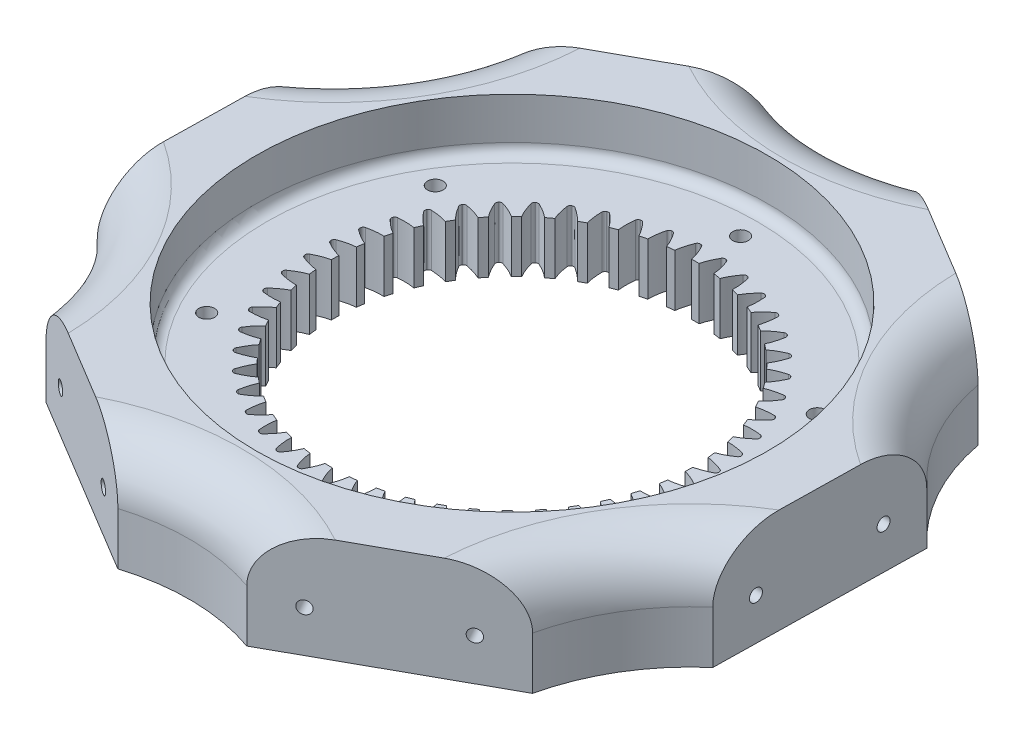
SolidWorks part; units mm, degrees
material "ABS"
ref_plane "Plan de face" through (0, 0, 0) normal (0, 0, 1) x (1, 0, 0)
ref_plane "Plan de dessus" through (0, 0, 0) normal (0, 1, 0) x (1, 0, 0)
ref_plane "Plan de droite" through (0, 0, 0) normal (1, 0, 0) x (0, 0, -1)
sketch "Esquisse1" plane through (0, 0, 0) normal (0, 1, 0) x (1, 0, 0)
  circle A0 centre (0, 0) radius 37.875
  circle A1 centre (0, 0) radius 34.5 construction
  circle A2 centre (0, 0) radius 36 construction
  circle A6 centre (0, 0) radius 33.8289 construction
  dimension "D1" = 72
  dimension "D5" = 1.875
  dimension "D6" = 1.5
  dimension "D7" = 67.6579
  dimension "D11" = 75.75
extrude "Boss.-Extru.1" add sketch "Esquisse1" along normal blind 10
sketch "Esquisse3" plane through (0, 0, 0) normal (0, 1, 0) x (1, 0, 0)
  spline S2 degree 4 poles (33.8289, 0) (33.8539, 0.0005) (33.924, 0.0037) (34.0563, 0.016) (34.2711, 0.0454) (34.5432, 0.0961) (34.8923, 0.177) (35.2997, 0.2918) (35.7425, 0.4383) (36.2181, 0.6191) (36.6866, 0.8186) (37.1478, 1.0347) (37.6016, 1.2659) (38.1432, 1.5633) (38.7827, 1.9461) (39.5113, 2.4268) (40.3185, 3.017) (41.1123, 3.6556) (41.8778, 4.3274) (42.6156, 5.0301) (43.2366, 5.6687) (43.7524, 6.2332) (44.2535, 6.8077) (44.662, 7.2997) (45.055, 7.7938) (45.4439, 8.3074) (45.7379, 8.7068) (46.0457, 9.1427) (46.3102, 9.5258) (46.689, 10.0991) (46.9096, 10.4462) (47.2576, 11.0073) (47.4044, 11.2615) (47.541, 11.4906) (47.5789, 11.5586) (47.6078, 11.6082) (47.6235, 11.635) knots 0 0 0 0 0 0.005377 0.015084 0.028532 0.04661 0.064855 0.092111 0.119476 0.146842 0.174209 0.201575 0.228941 0.256307 0.307035 0.361767 0.4165 0.471232 0.525964 0.580697 0.635429 0.662795 0.690161 0.744894 0.77226 0.799626 0.826992 0.854358 0.881725 0.909091 0.954545 0.977273 0.988636 0.994318 1 1 1 1 1 construction
  spline S3 degree 4 poles (33.8289, 0) (33.8539, 0.0005) (33.924, 0.0037) (34.0563, 0.016) (34.2711, 0.0454) (34.5432, 0.0961) (34.8923, 0.177) (35.2997, 0.2918) (35.7425, 0.4383) (36.2181, 0.6191) (36.6866, 0.8186) (37.1478, 1.0347) (37.6016, 1.2659) (38.1432, 1.5633) (38.7827, 1.9461) (39.5113, 2.4268) (40.3185, 3.017) (41.1123, 3.6556) (41.8778, 4.3274) (42.6156, 5.0301) (43.2366, 5.6687) (43.7524, 6.2332) (44.2535, 6.8077) (44.662, 7.2997) (45.055, 7.7938) (45.4439, 8.3074) (45.7379, 8.7068) (46.0457, 9.1427) (46.3102, 9.5258) (46.554, 9.8948) (46.6814, 10.0908) (46.7439, 10.1882) knots 0 0 0 0 0 0.005377 0.015084 0.028532 0.04661 0.064855 0.092111 0.119476 0.146842 0.174209 0.201575 0.228941 0.256307 0.307035 0.361767 0.4165 0.471232 0.525964 0.580697 0.635429 0.662795 0.690161 0.744894 0.77226 0.799626 0.826992 0.854358 0.881725 0.909091 0.909091 0.909091 0.909091 0.909091
sketch "Esquisse5" plane through (0, 0, 0) normal (0, 1, 0) x (1, 0, 0)
  line L0 (0, 0) -> (35.9943, -0.6415) construction
  circle A0 centre (0, 0) radius 34.5 construction
  arc A1 (34.4748, -1.3194) -> (34.4999, 0.0901) centre (0, 0) ccw
  circle A2 centre (0, 0) radius 36 construction
  spline S1 degree 4 poles (25.7599, 1999.7824) (28.1484, 36.3806) (30.2572, 0.6765) (32.2943, -0.2246) (34.2711, 0.0454) (34.5432, 0.0961) (34.8923, 0.177) (35.2997, 0.2918) (35.7425, 0.4383) (36.2181, 0.6191) (36.6866, 0.8186) (37.1478, 1.0347) (37.6016, 1.2659) (38.1432, 1.5633) (38.7827, 1.9461) (39.5113, 2.4268) (40.3185, 3.017) (41.1123, 3.6556) (41.8778, 4.3274) (42.6156, 5.0301) (43.2366, 5.6687) (43.7524, 6.2332) (44.2535, 6.8077) (44.662, 7.2997) (45.055, 7.7938) (45.4439, 8.3074) (45.7379, 8.7068) (46.0457, 9.1427) (47.3684, 11.0587) (50.4497, 16.1577) (14.6278, -39.0088) (1126.5221, 1693.5325) knots -0.382222 -0.382222 -0.382222 -0.382222 -0.382222 0.005377 0.015084 0.028532 0.04661 0.064855 0.092111 0.119476 0.146842 0.174209 0.201575 0.228941 0.256307 0.307035 0.361767 0.4165 0.471232 0.525964 0.580697 0.635429 0.662795 0.690161 0.744894 0.77226 0.799626 0.826992 0.854358 0.881725 1.347109 1.347109 1.347109 1.347109 1.347109 only from (33.8289, 0) to (46.7439, 10.1882) construction
  spline S2 degree 4 poles (34.4999, 0.0901) (34.5463, 0.0995) (34.6757, 0.127) (34.9277, 0.187) (35.2997, 0.2918) (35.7425, 0.4383) (36.2181, 0.6191) (36.6866, 0.8186) (37.1478, 1.0347) (37.6016, 1.2659) (38.1432, 1.5633) (38.7827, 1.9461) (39.5113, 2.4268) (40.3185, 3.017) (41.1123, 3.6556) (41.8778, 4.3274) (42.6156, 5.0301) (43.2366, 5.6687) (43.7524, 6.2332) (44.2535, 6.8077) (44.662, 7.2997) (45.055, 7.7938) (45.4439, 8.3074) (45.7379, 8.7068) (46.0457, 9.1427) (46.3102, 9.5258) (46.554, 9.8948) (46.6814, 10.0908) (46.7439, 10.1882) knots 0.036425 0.036425 0.036425 0.036425 0.036425 0.04661 0.064855 0.092111 0.119476 0.146842 0.174209 0.201575 0.228941 0.256307 0.307035 0.361767 0.4165 0.471232 0.525964 0.580697 0.635429 0.662795 0.690161 0.744894 0.77226 0.799626 0.826992 0.854358 0.881725 0.909091 0.909091 0.909091 0.909091 0.909091
  spline S3 degree 4 poles (34.4748, -1.3194) (34.5208, -1.3304) (34.6491, -1.3626) (34.8988, -1.4315) (35.2669, -1.5495) (35.7041, -1.7116) (36.173, -1.9093) (36.6342, -2.1253) (37.0873, -2.3577) (37.5326, -2.6049) (38.0633, -2.9215) (38.6887, -3.3269) (39.3997, -3.8332) (40.1854, -4.4518) (40.956, -5.1183) (41.697, -5.8169) (42.4093, -6.5455) (43.0071, -7.2058) (43.5025, -7.7883) (43.9828, -8.3803) (44.3736, -8.8866) (44.7487, -9.3943) (45.119, -9.9215) (45.3986, -10.3311) (45.6907, -10.7776) (45.9413, -11.1699) (46.1718, -11.5474) (46.2922, -11.7479) (46.3512, -11.8474) knots 0.036425 0.036425 0.036425 0.036425 0.036425 0.04661 0.064855 0.092111 0.119476 0.146842 0.174209 0.201575 0.228941 0.256307 0.307035 0.361767 0.4165 0.471232 0.525964 0.580697 0.635429 0.662795 0.690161 0.744894 0.77226 0.799626 0.826992 0.854358 0.881725 0.909091 0.909091 0.909091 0.909091 0.909091
  point P6 (35.996, 0.5365)
  dimension "D1" = 1.875
extrude "Enlèv. mat.-Extru.1" cut sketch "Esquisse5" against normal through all and the other way through all
fillet "Congé1" radius 0.57 2 edges at (37.775, 5, 2.751) (37.849, 5, -1.4032)
pattern_circular "Répétition circulaire1" count 48 over 360 about axis through (0, 10, 0) along (0, 1, 0) of "Enlèv. mat.-Extru.1", "Congé1"
sketch "Esquisse6" plane through (0, 0, 0) normal (0, -1, 0) x (1, 0, 0)
  circle A0 centre (0, 0) radius 49
  circle A1 centre (0, 0) radius 37.875 construction
  dimension "D1" = 11.125
  dimension "D2" = 98
extrude "Boss.-Extru.2" add sketch "Esquisse6" against normal up to surface (10 mm away) separate body up to face at (0, 10, 0)
combine bodies "Combiner1" operation type subtract main body 106 bodies to subtract 105
sketch "Esquisse8" plane through (0, 0, 0) normal (0, 1, 0) x (1, 0, 0)
  line L0 (-59.3732, 35.7047) -> (59.3732, -35.7047) construction
  line L1 (1.2346, 69.271) -> (-59.3732, 35.7047)
  line L2 (-59.3732, 35.7047) -> (-60.6078, -33.5663)
  line L3 (-60.6078, -33.5663) -> (-1.2346, -69.271)
  line L4 (-1.2346, -69.271) -> (59.3732, -35.7047)
  line L5 (59.3732, -35.7047) -> (60.6078, 33.5663)
  line L6 (60.6078, 33.5663) -> (1.2346, 69.271)
  line L7 (-60.6078, -33.5663) -> (60.6078, 33.5663) construction
  line L8 (1.2346, 69.271) -> (-1.2346, -69.271) construction
  circle A0 centre (0, 0) radius 49 construction
  circle A1 centre (0, 0) radius 49
  circle A2 centre (0, 0) radius 60 construction
  arc A3 (-29.1963, 18.38) -> (-29.9228, 17.1719) centre (0, 0) ccw construction
  point P13 (-29.5657, 17.7797)
  dimension "D1" = 120
extrude "Boss.-Extru.3" add sketch "Esquisse8" along normal blind 20
fillet "Congé2" radius 2 1 edges at (0, 10, 49)
sketch "Esquisse9" plane through (0, 20, 0) normal (0, 1, 0) x (1, 0, 0)
  line L0 (0, 0) -> (1.782, 99.9841) construction
  circle A0 centre (1.782, 99.9841) radius 40
  dimension "D1" = 100
  dimension "D2" = 80
extrude "Enlèv. mat.-Extru.2" cut sketch "Esquisse9" against normal through all
fillet "Congé3" radius 10 1 edges at (1.0692, 20, -59.9905)
sketch "Esquisse10" plane through (59.9905, 0, 1.0692) normal (0.9998, 0, 0.0178) x (0.0178, 0, -0.9998)
  line L0 (0, 0) -> (0, 20) construction
  line L1 (-34.641, 20) -> (34.641, 20) construction
  line L2 (-34.641, 0) -> (34.641, 0) construction
  circle A0 centre (-12, 8) radius 1.225
  circle A1 centre (12, 8) radius 1.225
  dimension "D1" = 24
  dimension "D2" = 2.45
  dimension "D3" = 8
extrude "Enlèv. mat.-Extru.3" cut sketch "Esquisse10" against normal blind 15
sketch "Esquisse13" plane through (0, 10, 0) normal (0, 1, 0) x (1, 0, 0)
  line L0 (0, 0) -> (0.891, 49.9921) construction
  circle A0 centre (0.7662, 42.9932) radius 1.5
  arc A2 (-22.3645, 56.2012) -> (24.353, 55.3685) centre (1.782, 99.9841) ccw construction
  dimension "D1" = 43
  dimension "D2" = 3
extrude "Enlèv. mat.-Extru.5" cut sketch "Esquisse13" against normal through all
pattern_circular "Répétition circulaire2" count 6 over 360 about axis through (0, 0, 0) along (0, 1, 0) of "Enlèv. mat.-Extru.2", "Enlèv. mat.-Extru.3", "Congé3", "Enlèv. mat.-Extru.5"
sketch "Esquisse11" plane through (0, 0, 0) normal (0, -1, 0) x (1, 0, 0)
  line L0 (29.0693, 52.4879) -> (0, 0) construction
  line L1 (11.4609, 62.2399) -> (46.6777, 42.7358) construction
  line L2 (0, 0) -> (-87.4798, 48.4488) construction
  circle A0 centre (-16.0027, 55.7307) radius 1.5
  arc A1 (-60.3492, 19.0562) -> (-48.1709, 41.0454) centre (-87.4798, 48.4488) ccw construction
  circle A2 centre (55.7307, 16.0027) radius 1.5
  circle A3 centre (16.0027, -55.7307) radius 1.5
  circle A4 centre (-55.7307, -16.0027) radius 1.5
  dimension "D1" = 82
  dimension "D2" = 82
  dimension "D3" = 3
extrude "Enlèv. mat.-Extru.4" cut sketch "Esquisse11" against normal blind 17
equation "\"D1@Esquisse1\"= \"Module\" * \"Z1\"'DP"
equation "\"Module\"= 1.5'module"
equation "\"Z1\"= 48'nb de dents"
equation "\"D5@Esquisse1\"= \"Module\" * 1.25'FondDeDent"
equation "\"D6@Esquisse1\"= \"Module\"'HauteurDeDent"
equation "\"a\"= 20'angle pression"
equation "\"D7@Esquisse1\"=\"D1@Esquisse1\"*cos( \"a\")"
equation "\"rayon\"= \"Module\" * 0.38'R fond de dent"
equation "\"D1@Esquisse5\"=360/\"Z1\"/4"
equation "\"D1@Répétition circulaire1\"= \"Z1\"'NbDents"
equation "\"D1@Congé1\"= \"rayon\"'R fond de dent"
